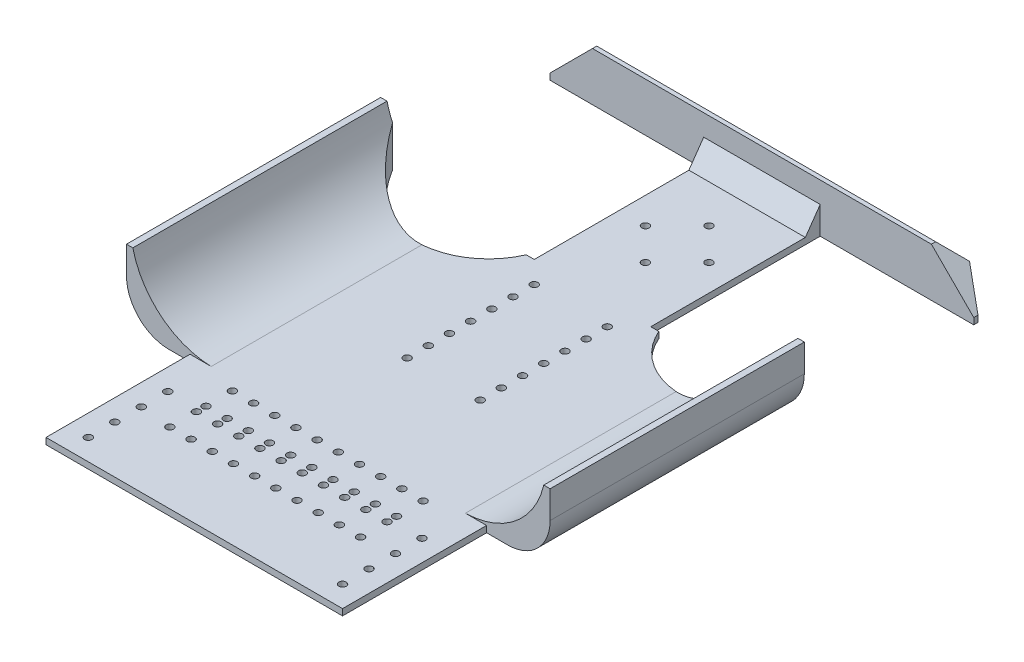
SolidWorks part; units mm, degrees
ref_plane "Front Plane" through (0, 0, 0) normal (0, 0, 1) x (1, 0, 0)
ref_plane "Top Plane" through (0, 0, 0) normal (0, 1, 0) x (1, 0, 0)
ref_plane "Right Plane" through (0, 0, 0) normal (1, 0, 0) x (0, 0, -1)
sketch "Sketch1" plane through (0, 0, 0) normal (0, 1, 0) x (1, 0, 0)
  line L6 (100, 60) -> (100, -60)
  line L7 (100, -60) -> (70, -60)
  line L8 (70, -60) -> (70, -128)
  line L11 (70, -128) -> (-70, -128)
  line L14 (-70, -128) -> (-70, -60)
  line L15 (-70, -60) -> (-100, -60)
  line L16 (-100, -60) -> (-100, 60)
  line L22 (-100, 60) -> (-27.5, 60)
  line L23 (27.5, 60) -> (100, 60)
  line L25 (27.5, 140) -> (100, 140)
  line L26 (100, 142) -> (100, 140)
  line L28 (-27.5, 140) -> (-100, 140)
  line L29 (-100, 140) -> (-100, 142)
  line L30 (100, 142) -> (70, 162)
  line L31 (70, 162) -> (-70, 162)
  line L32 (-70, 162) -> (-100, 142)
  line L33 (-27.5, 140) -> (-27.5, 60)
  line L35 (27.5, 140) -> (27.5, 60)
  line L37 (-27.5, 140) -> (27.5, 140) construction
  line L38 (0, 162) -> (0, 0) construction
  line L39 (-100, 140) -> (-100, 60) construction
  line L40 (100, 140) -> (100, 60) construction
  line L41 (-27.5, 60) -> (27.5, 60) construction
  line L42 (-70, -60) -> (70, -60) construction
  line L46 (0, 0) -> (0, -128) construction
  line L47 (100, 142) -> (-100, 142) construction
  point P14 (0, 140)
  point P30 (0, -60)
  dimension "D2" = 80
  dimension "D3" = 55
  dimension "D4" = 290
  dimension "D5" = 200
  dimension "D10" = 30
  dimension "D11" = 30
  dimension "D13" = 120
  dimension "D16" = 140
  dimension "D17" = 30
  dimension "D18" = 20
  dimension "D19" = 2
  dimension "D21" = 30
  dimension "D22" = 60
extrude "Boss-Extrude1" add sketch "Sketch1" along normal blind 3
sketch "Sketch8" plane through (0, 3, 0) normal (0, 1, 0) x (1, 0, 0)
  line L0 (-100, 140) -> (100, 140)
  line L1 (100, 140) -> (100, 142)
  line L2 (100, 142) -> (70, 162)
  line L3 (70, 162) -> (-70, 162)
  line L4 (-70, 162) -> (-100, 142)
  line L5 (-100, 142) -> (-100, 140)
extrude "Boss-Extrude2" add sketch "Sketch8" along normal blind 20
chamfer "Chamfer1" distance 20 angle 45 3 edges at (0, 23, -162) (-100, 23, -141) (100, 23, -141)
sketch "Sketch9" plane through (0, 3, 0) normal (0, 1, 0) x (1, 0, 0)
  line L0 (0, 0) -> (0, 100) construction
  line L1 (0, 100) -> (-15, 100) construction
  line L2 (0, 100) -> (15, 100) construction
  circle A0 centre (-15, 100) radius 1.75
  circle A1 centre (15, 100) radius 1.75
  circle A2 centre (0, 115) radius 1.75
  circle A3 centre (0, 85) radius 1.75
  dimension "D2" = 3.5
  dimension "D4" = 3.5
  dimension "D7" = 3.5
  dimension "D8" = 3.5
  dimension "D1" = 15
  dimension "D3" = 15
  dimension "D5" = 15
  dimension "D6" = 15
  dimension "D9" = 100
extrude "Cut-Extrude6" cut sketch "Sketch9" against normal through all
chamfer "Chamfer2" distance 10 angle 35 1 edges at (0, 3, -140)
sketch "Sketch12" plane through (0, 3, 0) normal (0, 1, 0) x (1, 0, 0)
  line L1 (-100, 60) -> (-60, 60)
  line L2 (-100, 60) -> (-100, -60)
  line L3 (-100, -60) -> (-60, -60)
  line L4 (-60, 60) -> (-60, -60)
  dimension "D1" = 120
  dimension "D2" = 40
extrude "Boss-Extrude3" add sketch "Sketch12" along normal blind 30
sketch "Sketch13" plane through (0, 0, 60) normal (0, 0, 1) x (1, 0, 0)
  line L0 (-100, 33) -> (-60, 33) construction
  line L1 (-97, 33) -> (-60, 33)
  line L2 (-60, 33) -> (-60, 3)
  arc A0 (-60, 3) -> (-97, 33) centre (-59.1368, 41.8813) cw
  dimension "D1" = 3
extrude "Cut-Extrude8" cut sketch "Sketch13" against normal blind 120
sketch "Sketch14" plane through (0, 0, 0) normal (0, -1, 0) x (1, 0, 0)
  line L0 (-100, -60) -> (-27.5, -60) construction
  line L1 (-31.3037, -60) -> (-94.3823, -60)
  arc A0 (-94.3823, -60) -> (-31.3037, -60) centre (-62.843, -73.7613) cw
extrude "Cut-Extrude9" cut sketch "Sketch14" against normal through all
mirror "Mirror3" about plane through (0, 0, 0) normal (1, 0, 0) of "Cut-Extrude9", "Boss-Extrude3", "Cut-Extrude8"
fillet "Fillet2" radius 20 2 edges at (-100, 0, 0) (100, 0, 0)
sketch "Sketch16" plane through (0, 3, 0) normal (0, 1, 0) x (1, 0, 0)
  line L0 (0, 0) -> (0, 49.7276) construction
  line L1 (-17.25, 49.7276) -> (17.25, 49.7276) construction
  circle A0 centre (-17.25, 49.7276) radius 1.75
  circle A1 centre (17.25, 49.7276) radius 1.75
  point P5 (0, 49.7276)
  dimension "D2" = 3.5
  dimension "D3" = 3.5
  dimension "D1" = 34.5
extrude "Cut-Extrude10" cut sketch "Sketch16" against normal through all
pattern_linear "LPattern1" count 7 spacing 10 along (0, 0, 1) of "Cut-Extrude10"
sketch "Sketch17" plane through (0, 3, 0) normal (0, 1, 0) x (1, 0, 0)
  line L0 (-60, -118) -> (-60, -93) construction
  line L1 (-70, -128) -> (-70, -60) construction
  line L2 (70, -128) -> (-70, -128) construction
  circle A0 centre (-60, -118) radius 1.75
  circle A1 centre (-60, -93) radius 1.75
  dimension "D2" = 3.5
  dimension "D3" = 3.5
  dimension "D1" = 25
  dimension "D4" = 10
  dimension "D5" = 10
extrude "Cut-Extrude11" cut sketch "Sketch17" against normal through all
pattern_linear "LPattern2" count 2 spacing 12.5 along (0, 0, -1) of "Cut-Extrude11"
mirror "Mirror4" about plane through (0, 0, 0) normal (1, 0, 0) of "LPattern2", "Cut-Extrude11"
sketch "Sketch18" plane through (0, 3, 0) normal (0, 1, 0) x (1, 0, 0)
  line L0 (-70, -128) -> (-70, -60) construction
  line L1 (70, -128) -> (-70, -128) construction
  line L2 (-45, -82) -> (-45, -65) construction
  circle A0 centre (-45, -82) radius 1.75
  circle A1 centre (-45, -65) radius 1.75
  dimension "D3" = 3.5
  dimension "D5" = 3.5
  dimension "D1" = 25
  dimension "D2" = 46
  dimension "D4" = 17
extrude "Cut-Extrude12" cut sketch "Sketch18" against normal through all
pattern_linear "LPattern3" count 10 spacing 10 along (1, 0, 0) of "Cut-Extrude12"
pattern_linear "LPattern4" count 2 spacing 12.5 along (0, 0, 1) of "LPattern3", "Cut-Extrude12"
